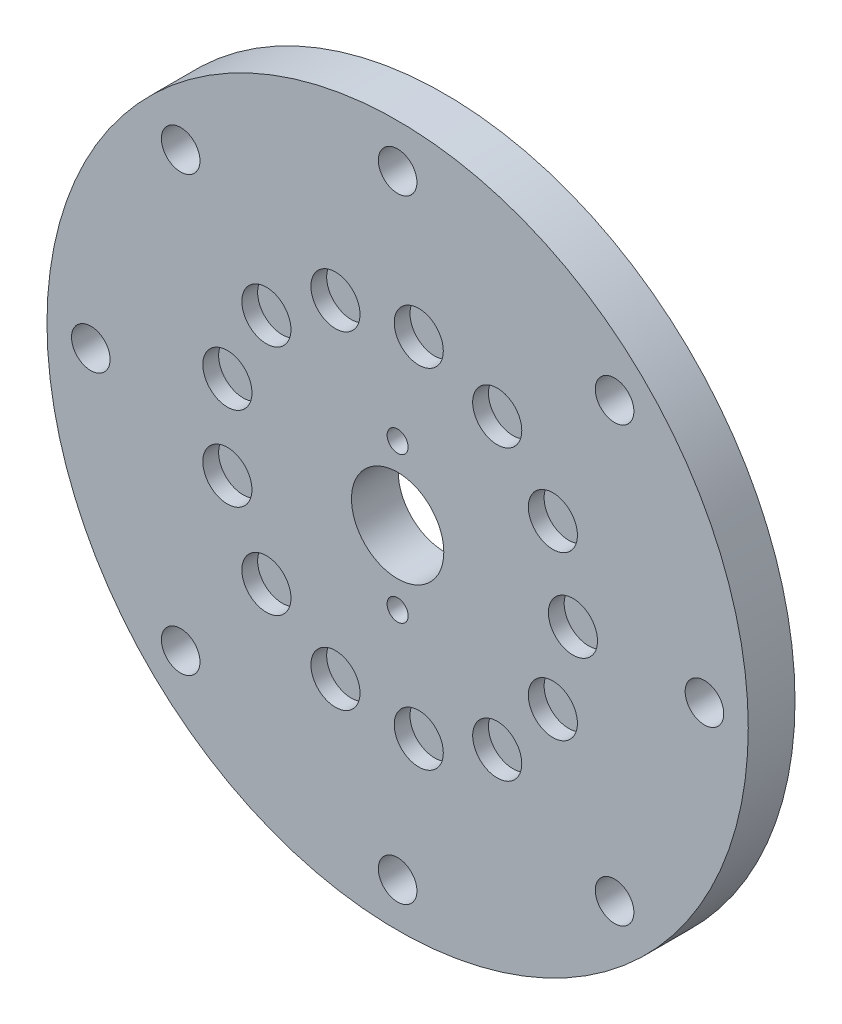
SolidWorks part; units mm, degrees
material "Polylactic Acid (PLA)"
ref_plane "Front Plane" through (0, 0, 0) normal (0, 0, 1) x (1, 0, 0)
ref_plane "Top Plane" through (0, 0, 0) normal (0, 1, 0) x (1, 0, 0)
ref_plane "Right Plane" through (0, 0, 0) normal (1, 0, 0) x (0, 0, -1)
sketch "Sketch1" plane through (0, 0, 0) normal (0, 0, 1) x (1, 0, 0)
  circle A0 centre (0, 0) radius 60
  circle A1 centre (0, 0) radius 7.9
  dimension "D1" = 120
  dimension "D2" = 15.8
extrude "Boss-Extrude1" add sketch "Sketch1" along normal blind 8
sketch "Sketch2" plane through (0, 0, 8) normal (0, 0, 1) x (1, 0, 0)
  circle A0 centre (0, 12.5) radius 1.7 construction
  circle A1 centre (0, 0) radius 12.5 construction
  circle A2 centre (0, -12.5) radius 1.7 construction
  point P0 (0, 12.5)
  point P8 (0, -12.5)
  point P10 (0, 0)
  dimension "D1" = 3.4
  dimension "D2" = 25
  dimension "D3" = 2
sketch "Sketch6" plane through (0, 0, 8) normal (0, 0, 1) x (1, 0, 0)
  circle A0 centre (0, 0) radius 52.5
  circle A1 centre (0, 0) radius 60 construction
  point P6 (0, 52.5)
  point P15 (37.1231, 37.1231)
  point P16 (52.5, 0)
  point P17 (37.1231, -37.1231)
  point P18 (0, -52.5)
  point P19 (-37.1231, -37.1231)
  point P20 (-52.5, 0)
  point P21 (-37.1231, 37.1231)
  dimension "D1" = 7.5
  dimension "D2" = 8
hole_wizard "M6 Clearance Hole1" positions "Sketch6" profile "Sketch5" hole size "M6" standard "ISO" end condition through all
sketch "Sketch5" plane through (-37.1231, 37.1231, 8) normal (1, 0, 0) x (0, -1, 0)
  line L0 (0, 0) -> (0, 8)
  line L1 (0, 8) -> (3.3, 8)
  line L2 (3.3, 8) -> (3.3, 0)
  line L5 (3.3, 0) -> (0, 0)
  line L11 (0, -6.35) -> (0, 107.95) construction
  dimension "Thru Hole Dia." = 6.6
  dimension "Thru Hole Depth" = 8
hole_wizard "M3 Clearance Hole1" positions "Sketch2" profile "Sketch7" hole size "M3" standard "ISO" end condition through all
sketch "Sketch7" plane through (0, 12.5, 8) normal (1, 0, 0) x (0, -1, 0)
  line L0 (0, 0) -> (0, 8)
  line L1 (0, 8) -> (1.8, 8)
  line L2 (1.8, 8) -> (1.8, 0)
  line L5 (1.8, 0) -> (0, 0)
  line L11 (0, -6.35) -> (0, 107.95) construction
  dimension "Thru Hole Dia." = 3.6
  dimension "Thru Hole Depth" = 8
sketch "Sketch8" plane through (0, 0, 8) normal (0, 0, 1) x (1, 0, 0)
  line L0 (-30, 0) -> (30, 0) construction
  line L1 (0, 0) -> (30, 0) construction
  line L2 (0, 0) -> (26.5637, -13.9417) construction
  circle A0 centre (0, 0) radius 30 construction
  circle A1 centre (30, 0) radius 4.2
  circle A2 centre (26.5637, -13.9417) radius 4.2
  circle A3 centre (17.0419, -24.6895) radius 4.2
  circle A4 centre (3.6161, -29.7813) radius 4.2
  circle A5 centre (-10.6381, -28.0505) radius 4.2
  circle A6 centre (-22.4553, -19.8937) radius 4.2
  circle A7 centre (-29.1283, -7.1795) radius 4.2
  circle A8 centre (-29.1283, 7.1795) radius 4.2
  circle A9 centre (-22.4553, 19.8937) radius 4.2
  circle A10 centre (-10.6381, 28.0505) radius 4.2
  circle A11 centre (3.6161, 29.7813) radius 4.2
  circle A12 centre (17.0419, 24.6895) radius 4.2
  circle A13 centre (26.5637, 13.9417) radius 4.2
  dimension "D1" = 60
  dimension "D2" = 8.4
  dimension "D4" = 27.692
  dimension "D3" = 13
extrude "Cut-Extrude1" cut sketch "Sketch8" against normal blind 2.7
